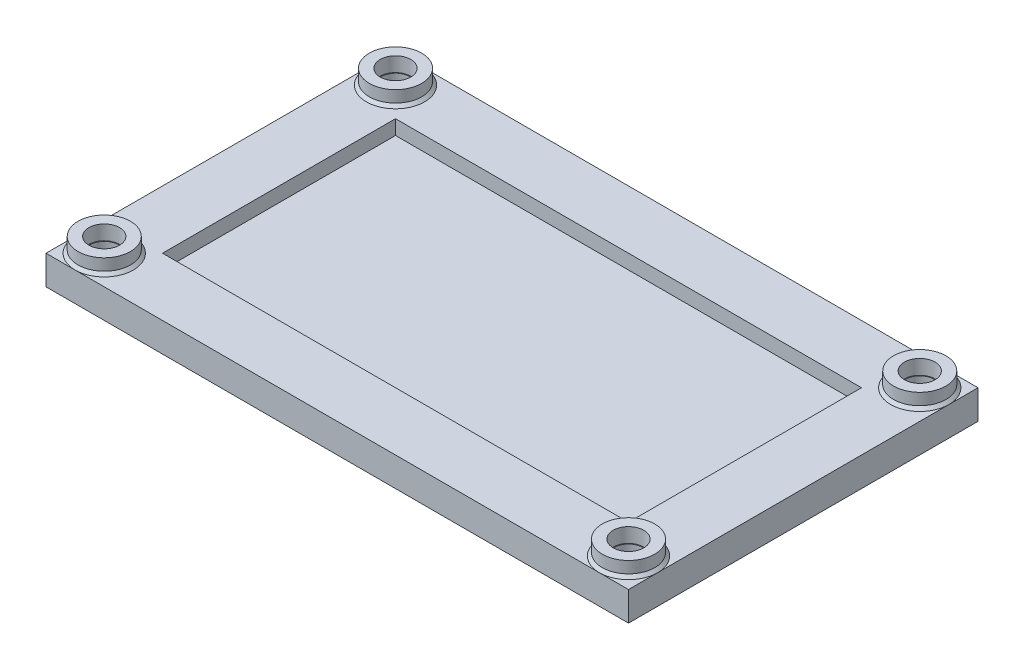
SolidWorks part; units mm, degrees
ref_plane "Front Plane" through (0, 0, 0) normal (0, 0, 1) x (1, 0, 0)
ref_plane "Top Plane" through (0, 0, 0) normal (0, 1, 0) x (1, 0, 0)
ref_plane "Right Plane" through (0, 0, 0) normal (1, 0, 0) x (0, 0, -1)
sketch "Sketch1" plane through (0, 0, 0) normal (0, 1, 0) x (1, 0, 0)
  line L1 (100, -60) -> (-100, -60)
  line L2 (100, -60) -> (100, 60)
  line L3 (100, 60) -> (-100, 60)
  line L4 (-100, -60) -> (-100, 60)
  line L5 (100, -60) -> (-100, 60) construction
  line L6 (100, 60) -> (-100, -60) construction
  point P0 (0, 0)
  dimension "D1" = 200
  dimension "D2" = 120
extrude "Boss-Extrude3" add sketch "Sketch1" along normal blind 10
sketch "Sketch3" plane through (0, 10, 0) normal (0, 1, 0) x (1, 0, 0)
  line L0 (-100, 60) -> (-80, 40) construction
  line L1 (-80, 40) -> (80, 40)
  line L2 (-80, 40) -> (-80, -40)
  line L3 (-80, -40) -> (80, -40)
  line L4 (80, 40) -> (80, -40)
  line L5 (-80, 40) -> (80, -40) construction
  line L6 (-80, -40) -> (80, 40) construction
  line L7 (80, 40) -> (100, 60) construction
  line L8 (-80, -40) -> (-100, -60) construction
  line L12 (80, -40) -> (100, -60) construction
  circle A0 centre (-90, 50) radius 5
  circle A2 centre (90, -50) radius 5
  circle A4 centre (90, 50) radius 5
  circle A5 centre (-90, -50) radius 5
  point P0 (0, 0)
  dimension "D3" = 10
  dimension "D4" = 10
  dimension "D5" = 10
  dimension "D6" = 10
  dimension "D1" = 160
  dimension "D2" = 80
extrude "Cut-Extrude2" cut sketch "Sketch3" along direction (0, 1, 0) on the side against the normal blind 5
sketch "Sketch6" plane through (0, 5, 0) normal (0, 1, 0) x (1, 0, 0)
  line L0 (-137.6039, 0) -> (193.2143, 0) construction
  line L1 (0, 104.4387) -> (0, -99.9573) construction
  circle A0 centre (-90, 50) radius 5.25
  circle A1 centre (90, 50) radius 5.25
  circle A2 centre (90, -50) radius 5.25
  circle A3 centre (-90, -50) radius 5.25
  circle A4 centre (-90, 50) radius 5.25
  circle A5 centre (-90, 50) radius 9
  circle A6 centre (90, 50) radius 5.25
  circle A7 centre (90, 50) radius 9
  circle A8 centre (90, -50) radius 9
  circle A9 centre (90, -50) radius 5.25
  circle A10 centre (-90, -50) radius 5.25
  circle A11 centre (-90, -50) radius 9
  circle M1 centre (-90, 50) radius 5
  dimension "D1" = 18
extrude "Boss-Extrude4" add sketch "Sketch6" along normal blind 10 contours A5 M1 | A7 A1 | A8 A2 | A11 A3 region at (-98.7454, 5, -50) region at (81.2546, 5, -50) region at (81.2546, 5, 50) region at (-98.7454, 5, 50)
chamfer "Chamfer1" distance 1 angle 45 4 edges at (90, 10, -41) (-90, 10, -41) (-90, 10, 59) (90, 10, 59)
